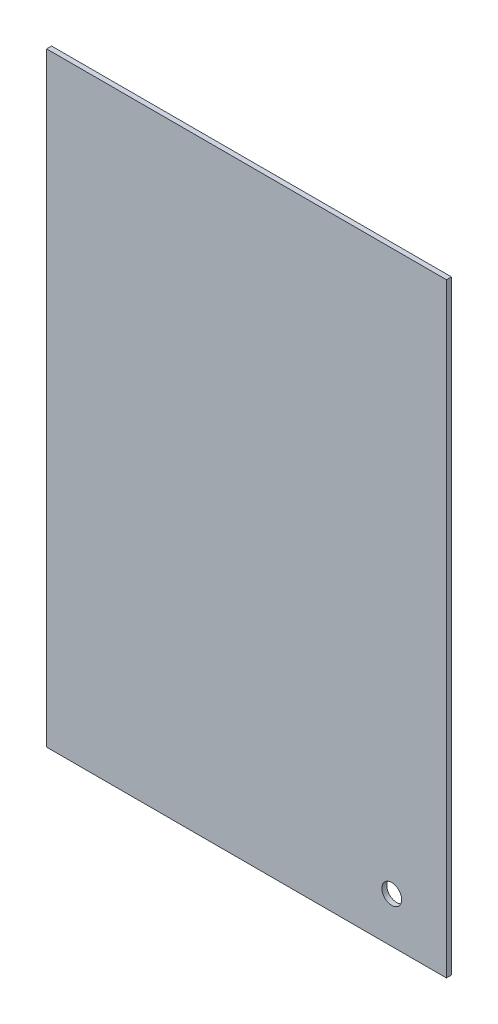
SolidWorks part; units mm, degrees
ref_plane "Alzado" through (0, 0, 0) normal (0, 0, 1) x (1, 0, 0)
ref_plane "Planta" through (0, 0, 0) normal (0, 1, 0) x (1, 0, 0)
ref_plane "Vista lateral" through (0, 0, 0) normal (1, 0, 0) x (0, 0, -1)
sketch "Sketch1" plane through (0, 0, 0) normal (0, 0, 1) x (1, 0, 0)
  line L1 (-121, 183) -> (121, 183)
  line L2 (-121, 183) -> (-121, -183)
  line L3 (-121, -183) -> (121, -183)
  line L4 (121, 183) -> (121, -183)
  line L5 (-121, 183) -> (121, -183) construction
  line L6 (-121, -183) -> (121, 183) construction
  point P0 (0, 0)
  dimension "D1" = 242
  dimension "D2" = 366
extrude "Boss-Extrude1" add sketch "Sketch1" along normal blind 3
sketch "Sketch2" plane through (0, 0, 3) normal (0, 0, 1) x (1, 0, 0)
  circle A0 centre (87.9, -155.5) radius 6
  dimension "D1" = 12
extrude "Cut-Extrude1" cut sketch "Sketch2" against normal up to next
